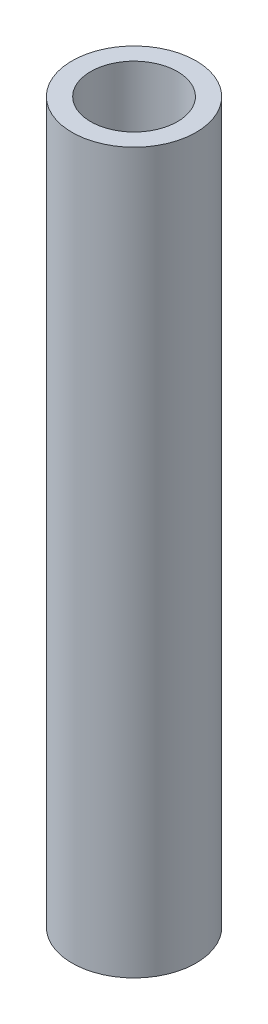
SolidWorks part; units mm, degrees
ref_plane "Front Plane" through (0, 0, 0) normal (0, 0, 1) x (1, 0, 0)
ref_plane "Top Plane" through (0, 0, 0) normal (0, 1, 0) x (1, 0, 0)
ref_plane "Right Plane" through (0, 0, 0) normal (1, 0, 0) x (0, 0, -1)
ref_axis "X" through (-88.99, 0, 0) along (1, 0, 0)
ref_axis "Y" through (0, 55, 0) along (0, -1, 0)
ref_axis "Z" through (0, 0, -88.99) along (0, 0, 1)
sketch "Sketch1" plane through (0, 0, 0) normal (0, 1, 0) x (1, 0, 0)
  circle A0 centre (0, 0) radius 5
  circle A1 centre (0, 0) radius 3.5
  dimension "D1" = 10
  dimension "D2" = 7
extrude "Boss-Extrude1" add sketch "Sketch1" along normal mid plane 58
